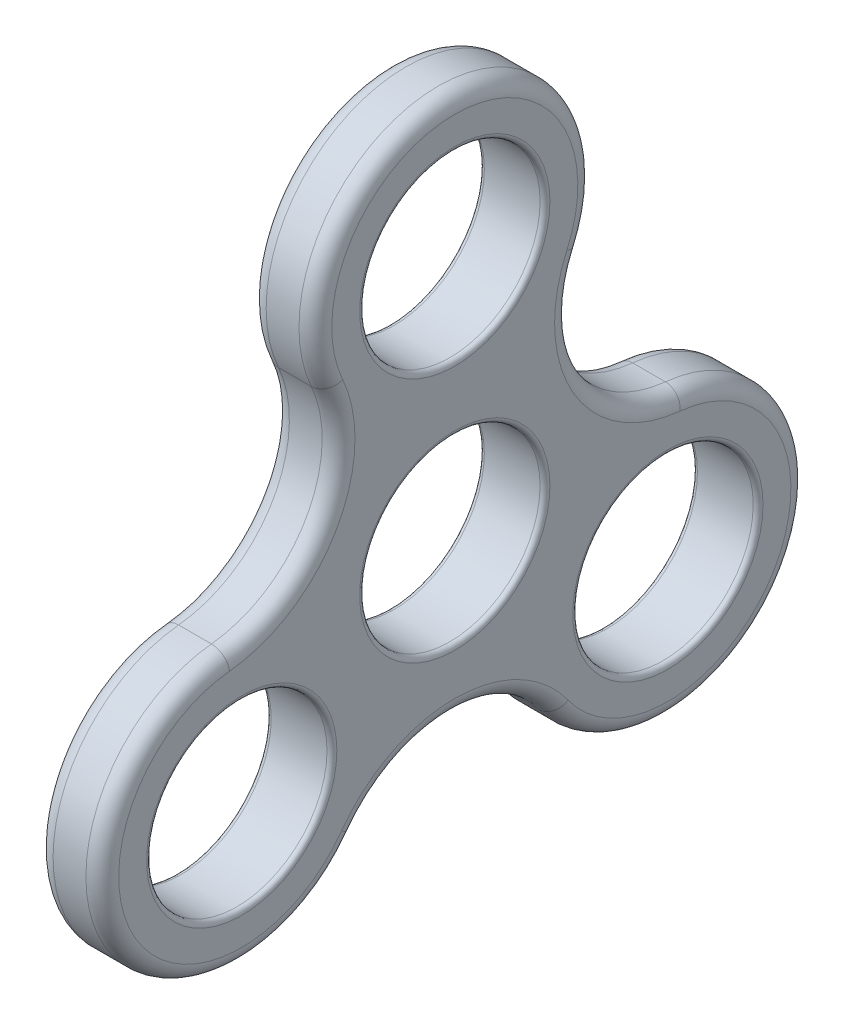
SolidWorks part; units mm, degrees
ref_plane "前视基准面" through (0, 0, 0) normal (0, 0, 1) x (1, 0, 0)
ref_plane "上视基准面" through (0, 0, 0) normal (0, 1, 0) x (1, 0, 0)
ref_plane "右视基准面" through (0, 0, 0) normal (1, 0, 0) x (0, 0, -1)
sketch "草图1" plane through (0, 0, 0) normal (1, 0, 0) x (0, 0, -1)
  line L0 (0, 30) -> (0, 0) construction
  line L1 (0, 0) -> (-25.9808, -15) construction
  line L2 (-25.9808, -15) -> (0, 0) construction
  line L3 (0, 0) -> (25.9808, -15) construction
  circle A0 centre (0, 0) radius 11
  circle A1 centre (0, 30) radius 11
  circle A2 centre (0, 30) radius 17
  circle A3 centre (25.9808, -15) radius 17
  circle A4 centre (-25.9808, -15) radius 17
  circle A5 centre (25.9808, -15) radius 11
  circle A6 centre (-25.9808, -15) radius 11
  arc A7 (15.4961, 23.0092) -> (27.6746, 1.9154) centre (29.1691, 16.8408) ccw
  arc A8 (-15.4961, 23.0092) -> (-27.6746, 1.9154) centre (-29.1691, 16.8408) cw
  arc A9 (-12.1785, -24.9246) -> (12.1785, -24.9246) centre (0, -33.6815) cw
  point P5 (-16.4545, -9.5)
  point P8 (16.4545, -9.5)
  point P14 (0, 0)
  point P19 (0, 0)
  point P27 (-15.4961, 23.0092)
  point P28 (0, 0)
  point P29 (0, 0)
  dimension "D1" = 22
  dimension "D8" = 15
  dimension "D2" = 30
  dimension "D6" = 120
  dimension "D7" = 120
  dimension "D3" = 6
  dimension "D4" = 3
  dimension "D5" = 3
extrude "凸台-拉伸1" add sketch "草图1" along normal mid plane 8 contours A2 A1 | A4 A9 A3 A7 A2 A8 A0 | A4 A6 | A3 A5 region at (0, 26.5257, -16.1497) region at (0, 12.2678, 0) region at (0, -2.7511, 14.8971) region at (0, -3.9164, -38.2297)
fillet "圆角1" radius 2 12 edges at (-4, 47, 0) (-4, 9.3408, -16.1787) (-4, -23.5, -40.7032) (-4, -18.6815, 0) (-4, -23.5, 40.7032) (4, 47, 0) (4, 9.3408, -16.1787) (4, -23.5, -40.7032) (4, -18.6815, 0) (4, -23.5, 40.7032) (-4, 9.3408, 16.1787) (4, 9.3408, 16.1787)
fillet "圆角2" radius 0.6 8 edges at (-4, -15, 14.9808) (4, -15, 14.9808) (-4, -15, -36.9808) (4, -15, -36.9808) (-4, 0, -11) (4, 0, -11) (-4, 30, -11) (4, 30, -11)
ref_axis "基准轴1" through (3.4, 0, 0) along (-1, 0, 0)
